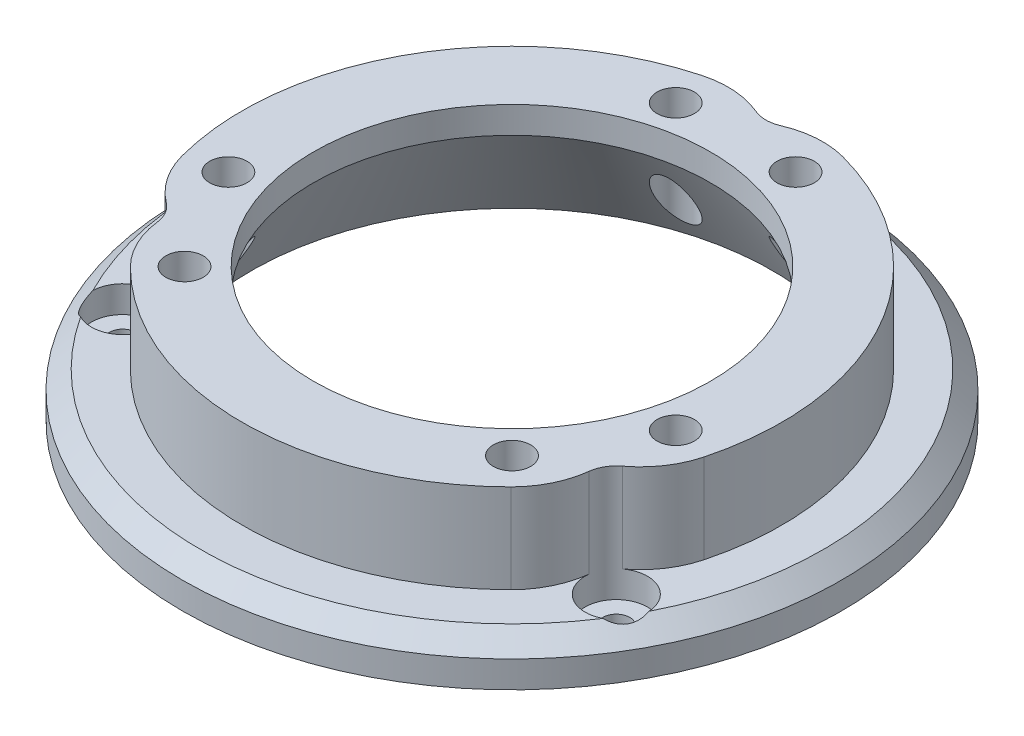
SolidWorks part; units mm, degrees
ref_plane "Front Plane" through (0, 0, 0) normal (0, 0, 1) x (1, 0, 0)
ref_plane "Top Plane" through (0, 0, 0) normal (0, 1, 0) x (1, 0, 0)
ref_plane "Right Plane" through (0, 0, 0) normal (1, 0, 0) x (0, 0, -1)
sketch "Sketch1" plane through (0, 0, 0) normal (0, 1, 0) x (1, 0, 0)
  circle A0 centre (0, 0) radius 30.3
  circle A1 centre (0, 0) radius 22.3
  dimension "D1" = 60.6
  dimension "D2" = 8
extrude "Boss-Extrude1" add sketch "Sketch1" along normal blind 10
sketch "Sketch2" plane through (0, 0, 0) normal (0, 1, 0) x (1, 0, 0)
  circle A0 centre (0, 0) radius 37
  circle A1 centre (0, 0) radius 22.3
  circle A2 centre (0, 0) radius 22.3 construction
  dimension "D1" = 74
extrude "Boss-Extrude2" add sketch "Sketch2" against normal blind 5
sketch "Sketch3" plane through (0, 0, 0) normal (0, 1, 0) x (1, 0, 0)
  circle A0 centre (0, 32) radius 1.5
  dimension "D2" = 3
  dimension "D1" = 32
extrude "Cut-Extrude1" cut sketch "Sketch3" against normal through all
sketch "Sketch4" plane through (0, 0, 0) normal (0, 1, 0) x (1, 0, 0)
  circle A0 centre (0, 32) radius 3.5
  dimension "D1" = 7
extrude "Cut-Extrude2" cut sketch "Sketch4" against normal blind 3 and the other way through all
pattern_circular "CirPattern1" count 3 over 360 about axis through (0, -5, 0) along (0, 1, 0) of "Cut-Extrude1", "Cut-Extrude2"
chamfer "Chamfer1" distance 12 angle 30 1 edges at (0, -5, 22.3) first distance on face at (0, 10, 22.3)
chamfer "Chamfer2" distance 2 angle 45 1 edges at (0, 0, 37)
sketch "Sketch5" plane through (0, 10, 0) normal (0, 1, 0) x (1, 0, 0)
  line L0 (6.7293, 25.1141) -> (0, 0) construction
  line L1 (0, 0) -> (0, 32) construction
  circle A0 centre (6.7293, 25.1141) radius 2.1
  circle A1 centre (-6.7293, 25.1141) radius 2.1
  dimension "D2" = 4.2
  dimension "D1" = 15
  dimension "D3" = 26
extrude "Cut-Extrude3" cut sketch "Sketch5" against normal through all
pattern_circular "CirPattern2" count 3 over 360 about axis through (0, 10, 0) along (0, -1, 0) of "Cut-Extrude3" reverse direction yes
fillet "Fillet1" radius 10 6 edges at (27.6006, 5, 12.5018) (24.6272, 5, 17.652) (-24.6272, 5, 17.652) (-27.6006, 5, 12.5018) (-2.9734, 5, -30.1537) (2.9734, 5, -30.1537)
